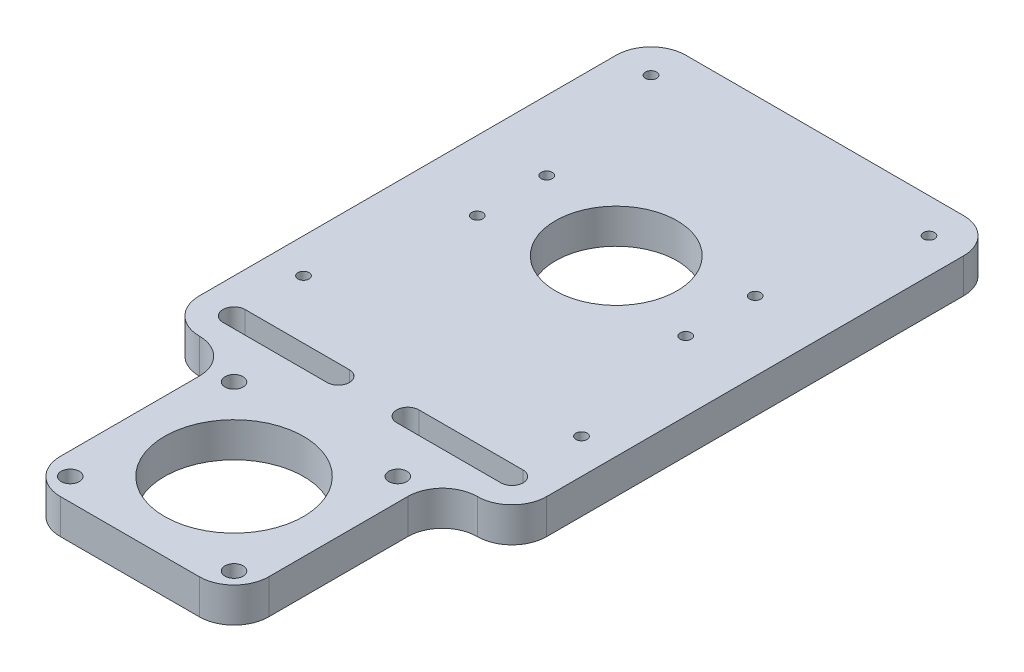
SolidWorks part; units mm, degrees
material "Acrylic (Medium-high impact)"
ref_plane "Front Plane" through (0, 0, 0) normal (0, 0, 1) x (1, 0, 0)
ref_plane "Top Plane" through (0, 0, 0) normal (0, 1, 0) x (1, 0, 0)
ref_plane "Right Plane" through (0, 0, 0) normal (1, 0, 0) x (0, 0, -1)
sketch "Sketch1" plane through (0, 0, 0) normal (0, 1, 0) x (1, 0, 0)
  line L0 (-50, -80) -> (-50, -140) construction
  line L1 (-50, 60) -> (50, 60)
  line L2 (-50, 60) -> (-50, -80)
  line L3 (-50, -80) -> (-30, -80)
  line L4 (50, 60) -> (50, -80)
  line L5 (-30, -140) -> (30, -140)
  line L6 (50, -140) -> (50, -80) construction
  line L7 (-30, -80) -> (-30, -140)
  line L8 (30, -80) -> (30, -140)
  line L9 (-50, -140) -> (-30, -140) construction
  line L10 (30, -140) -> (50, -140) construction
  line L11 (-30, -80) -> (30, -80) construction
  line L12 (30, -80) -> (50, -80)
  dimension "D1" = 60
  dimension "D2" = 80
  dimension "D3" = 60
  dimension "D4" = 100
  dimension "D5" = 50
  dimension "D6" = 20
  dimension "D7" = 20
extrude "Boss-Extrude1" add sketch "Sketch1" along normal blind 10
sketch "Sketch2" plane through (0, 10, 0) normal (0, 1, 0) x (1, 0, 0)
  line L0 (-40, -130) -> (40, -130) construction
  line L1 (-40, -50) -> (40, -50) construction
  line L2 (-40, -50) -> (-40, 50) construction
  line L3 (-40, 50) -> (40, 50) construction
  line L4 (40, -50) -> (40, 50) construction
  line L5 (-40, -50) -> (40, 50) construction
  line L6 (-40, 50) -> (40, -50) construction
  line L7 (-30, -140) -> (30, -140) construction
  line L8 (0, -50) -> (0, -130) construction
  line L9 (-40, -130) -> (-40, -100) construction
  line L10 (-40, -100) -> (40, -100) construction
  line L11 (40, -100) -> (40, -130) construction
  circle A0 centre (0, 0) radius 17.5
  circle A1 centre (-40, -50) radius 1.6
  circle A2 centre (40, -50) radius 1.6
  circle A3 centre (40, 50) radius 1.6
  circle A4 centre (-40, 50) radius 1.6
  circle A5 centre (-40, -130) radius 1.6
  circle A6 centre (40, -130) radius 1.6
  circle A7 centre (-40, -100) radius 1.6
  circle A8 centre (40, -100) radius 1.6
  dimension "D1" = 35
  dimension "D2" = 3.2
  dimension "D5" = 10
  dimension "D7" = 30
  dimension "D3" = 100
  dimension "D4" = 80
  dimension "D6" = 80
extrude "Cut-Extrude1" cut sketch "Sketch2" against normal through all both and the other way through all
sketch "Sketch3" plane through (0, 10, 0) normal (0, 1, 0) x (1, 0, 0)
  line L0 (0, 0) -> (0, -110) construction
  line L1 (-23.57, -133.57) -> (23.57, -133.57) construction
  line L2 (-23.57, -133.57) -> (-23.57, -86.43) construction
  line L3 (-23.57, -86.43) -> (23.57, -86.43) construction
  line L4 (23.57, -133.57) -> (23.57, -86.43) construction
  line L5 (-23.57, -133.57) -> (23.57, -86.43) construction
  line L6 (-23.57, -86.43) -> (23.57, -133.57) construction
  line L7 (-40, -70) -> (-10, -70) construction
  line L14 (-40, -66.8) -> (-10, -66.8)
  line L15 (-40, -73.2) -> (-10, -73.2)
  line L16 (-50, 60) -> (-50, -80) construction
  line L17 (-50, -80) -> (-30, -80) construction
  line L18 (40, -70) -> (10, -70) construction
  line L19 (40, -66.8) -> (10, -66.8)
  line L20 (40, -73.2) -> (10, -73.2)
  circle A0 centre (0, -110) radius 20
  circle A1 centre (-23.57, -86.43) radius 2.6
  circle A2 centre (23.57, -86.43) radius 2.6
  circle A3 centre (23.57, -133.57) radius 2.6
  circle A4 centre (-23.57, -133.57) radius 2.6
  arc A7 (-40, -66.8) -> (-40, -73.2) centre (-40, -70) ccw
  arc A8 (-10, -73.2) -> (-10, -66.8) centre (-10, -70) ccw
  arc A9 (40, -66.8) -> (40, -73.2) centre (40, -70) cw
  arc A10 (10, -73.2) -> (10, -66.8) centre (10, -70) cw
  point P0 (0, -110)
  point P15 (-25, -70)
  point P26 (25, -70)
  dimension "D1" = 40
  dimension "D4" = 5.2
  dimension "D2" = 47.14
  dimension "D3" = 110
  dimension "D5" = 10
  dimension "D6" = 10
  dimension "D7" = 10
  dimension "D8" = 6.4
extrude "Cut-Extrude2" cut sketch "Sketch3" against normal through all both and the other way through all
sketch "Sketch4" plane through (0, 10, 0) normal (0, 1, 0) x (1, 0, 0)
  line L1 (-30, -10) -> (30, -10) construction
  line L2 (-30, -10) -> (-30, 10) construction
  line L3 (-30, 10) -> (30, 10) construction
  line L4 (30, -10) -> (30, 10) construction
  line L5 (-30, -10) -> (30, 10) construction
  line L6 (-30, 10) -> (30, -10) construction
  circle A0 centre (-30, 10) radius 1.6
  circle A1 centre (-30, -10) radius 1.6
  circle A2 centre (30, 10) radius 1.6
  circle A3 centre (30, -10) radius 1.6
  point P0 (0, 0)
  dimension "D3" = 3.2
  dimension "D1" = 20
  dimension "D2" = 60
extrude "Cut-Extrude3" cut sketch "Sketch4" against normal through all both and the other way through all
fillet "Fillet1" radius 10 8 edges at (50, 5, -60) (-50, 5, -60) (-30, 5, 80) (-30, 5, 140) (30, 5, 140) (30, 5, 80) (50, 5, 80) (-50, 5, 80)
